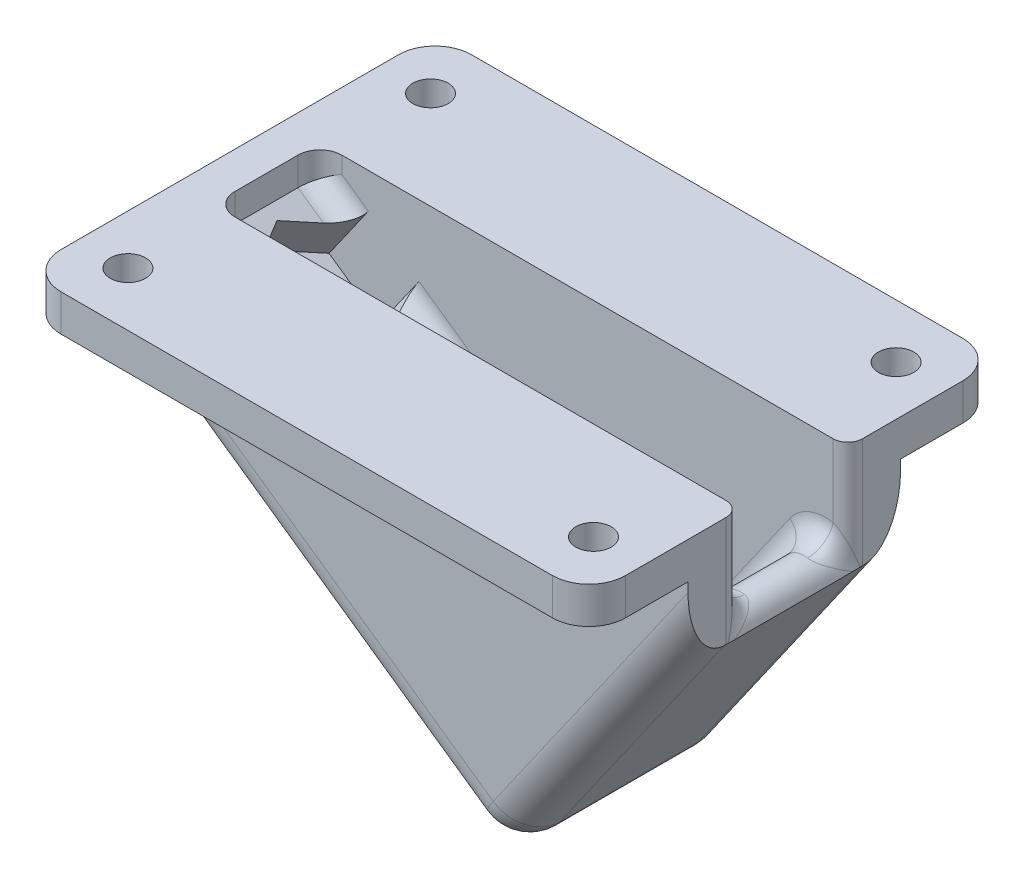
SolidWorks part; units mm, degrees
ref_plane "Front Plane" through (0, 0, 0) normal (0, 0, 1) x (1, 0, 0)
ref_plane "Top Plane" through (0, 0, 0) normal (0, 1, 0) x (1, 0, 0)
ref_plane "Right Plane" through (0, 0, 0) normal (1, 0, 0) x (0, 0, -1)
sketch "Sketch2" plane through (0, 0, 0) normal (0, 0, 1) x (1, 0, 0)
  line L0 (-38.5, 0) -> (38.5, 0)
  line L3 (-38.5, 0) -> (-38.5, -15)
  line L4 (-38.5, -15) -> (13.1678, -51.1782)
  line L5 (13.1678, -51.1782) -> (38.5, -15)
  line L6 (38.5, -15) -> (38.5, 0)
  line L7 (-23.3644, -10.9488) -> (-30.2473, -20.7786) construction
  line L8 (-33.5, -3.8517) -> (15.9549, -38.4805)
  line L9 (15.9549, -38.4805) -> (38.5, -6.2828)
  line L10 (9.4017, -33.8918) -> (2.5188, -43.7217) construction
  line L11 (-33.5, -3.8517) -> (-33.5, 0)
  point P10 (8.8091, -38.36)
  dimension "D1" = 35
  dimension "D2" = 15
  dimension "D3" = 12
  dimension "D4" = 77
  dimension "D5" = 5
  dimension "D6" = 40
  dimension "D7" = 5
  dimension "D8" = 8
extrude "Boss-Extrude1" add sketch "Sketch2" along normal mid plane 29 contours L8 L11 L0 L3 L4 L5 L6 L9 | L11 L8 L9 L6 L0 region at (-4.1511, -26.2748, 0) region at (6.6072, -13.0013, 0)
extrude "Cut-Extrude1" cut sketch "Sketch2<4>" against normal mid plane 14.6 contours L11 L8 L9 L6 L0 region at (6.6072, -13.0013, 0)
sketch "Sketch2<4>" plane through (0, 0, 0) normal (0, 0, 1) x (1, 0, 0) same geometry as "Sketch2"
sketch "Sketch3" plane through (0, 0, 0) normal (0, 1, 0) x (1, 0, 0)
  line L0 (38.5, -14.5) -> (38.5, -7.3) construction
  line L1 (-38.5, 28) -> (38.5, 28)
  line L2 (-38.5, 28) -> (-38.5, -28)
  line L3 (-38.5, -28) -> (38.5, -28)
  line L4 (38.5, 28) -> (38.5, -28)
  line L5 (-38.5, -14.5) -> (-38.5, 14.5) construction
  line L6 (-31.75, 20.6375) -> (31.75, -20.6375) construction
  line L7 (-31.75, 20.6375) -> (31.75, 20.6375) construction
  line L8 (-31.75, 20.6375) -> (-31.75, -20.6375) construction
  line L9 (-31.75, -20.6375) -> (31.75, -20.6375) construction
  line L10 (31.75, 20.6375) -> (31.75, -20.6375) construction
  line L11 (-38.5, 14.5) -> (38.5, 14.5) construction
  line L12 (-38.5, 14.5) -> (38.5, 14.5)
  line L13 (-38.5, -14.5) -> (38.5, -14.5) construction
  line L14 (-38.5, -14.5) -> (38.5, -14.5)
  circle A0 centre (-31.75, 20.6375) radius 2.413
  circle A1 centre (-31.75, -20.6375) radius 2.413
  circle A2 centre (31.75, 20.6375) radius 2.413
  circle A3 centre (31.75, -20.6375) radius 2.413
  point P9 (-38.5, 0)
  point P18 (31.75, 20.6375)
  point P19 (31.75, -20.6375)
  line M8 (38.5, 14.5) -> (-38.5, 14.5)
  line M10 (-38.5, -14.5) -> (38.5, -14.5)
  dimension "D2" = 4.826
  dimension "D1" = 56
  dimension "D3" = 41.275
  dimension "D4" = 63.5
extrude "Boss-Extrude2" add sketch "Sketch3" against normal blind 5 contours L4 L1 L2 A2 A0 M8 | L4 L2 L3 A3 A1 M10 region at (0, 0, -21.2723) region at (0, 0, 21.2723)
sketch "Sketch4" plane through (-12.8309, -18.3244, 0) normal (0.5736, 0.8192, 0) x (0.8192, -0.5736, 0)
  line L0 (-15.0457, 0) -> (24.9543, 0) construction
  line L1 (-25.2323, 7.3) -> (35.141, -7.3) construction
  line L3 (-10.831, -7.3) -> (-6.6163, 0)
  line L4 (-6.6163, 0) -> (-10.831, 7.3)
  line L5 (-10.831, 7.3) -> (-19.2603, 7.3)
  line L6 (-19.2603, 7.3) -> (-23.475, 0)
  line L7 (-23.475, 0) -> (-19.2603, -7.3)
  line L8 (-19.2603, -7.3) -> (-10.831, -7.3)
  line L9 (33.3837, 0) -> (29.169, 7.3)
  line L10 (29.169, 7.3) -> (20.7397, 7.3)
  line L11 (20.7397, 7.3) -> (16.525, 0)
  line L12 (16.525, 0) -> (20.7397, -7.3)
  line L13 (20.7397, -7.3) -> (29.169, -7.3)
  line L14 (29.169, -7.3) -> (33.3837, 0)
  circle A0 centre (-15.0457, 0) radius 4.9
  circle A1 centre (24.9543, 0) radius 4.9
  circle A2 centre (-15.0457, 0) radius 7.3 construction
  circle A3 centre (24.9543, 0) radius 7.3 construction
  point P9 (4.9543, 0)
  dimension "D2" = 9.8
  dimension "D1" = 40
  dimension "D3" = 14.6
extrude "Cut-Extrude2" cut sketch "Sketch4" against normal blind 6.35
extrude "Cut-Extrude3" cut sketch "Sketch4<2>" against normal through all contours A0 | A1
sketch "Sketch4<2>" plane through (-12.8309, -18.3244, 0) normal (0.5736, 0.8192, 0) x (0.8192, -0.5736, 0) same geometry as "Sketch4"
fillet "Fillet1" radius 3 2 edges at (38.5, -6.2828, 0) (15.9549, -38.4805, 0)
fillet "Fillet2" radius 5 4 edges at (-38.5, -2.5, 28) (-38.5, -2.5, -28) (38.5, -2.5, -28) (38.5, -2.5, 28)
fillet "Fillet3" radius 5 1 edges at (13.1678, -51.1782, 0)
fillet "Fillet4" radius 5 7 edges at (27.2678, -31.0412, -14.5) (12.8081, -49.1386, -14.5) (27.2678, -31.0412, 14.5) (12.8081, -49.1386, 14.5) (-14.714, -31.6551, -14.5) (-14.714, -31.6551, 14.5) (-38.5, -15, 0)
fillet "Fillet5" radius 2 2 edges at (38.5, -7.5, -7.3) (38.5, -7.5, 7.3)
fillet "Fillet6" radius 3 16 edges at (12.2802, -35.9074, 7.3) (15.7392, -37.2567, 7.3) (37.7403, -13.8022, 7.731) (34.5847, -12.9406, 7.3) (37.3528, -13.4381, -7.4909) (34.5847, -12.9406, -7.3) (25.3591, -25.0499, -7.3) (15.7392, -37.2567, -7.3) (-33.5, -1.9259, 7.3) (-33.5, -1.9259, -7.3) (-31.054, -5.5644, -7.3) (-31.054, -5.5644, 7.3) (-8.7725, -21.1661, 7.3) (25.3591, -25.0499, 7.3) (-8.7725, -21.1661, -7.3) (12.2802, -35.9074, -7.3)
